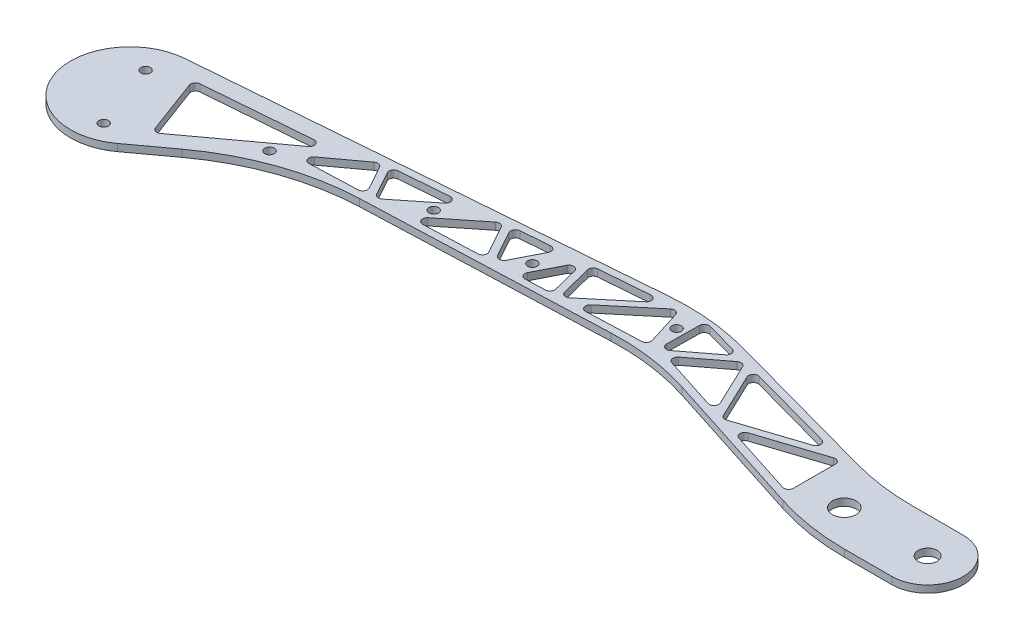
SolidWorks part; units mm, degrees
ref_plane "Front Plane" through (0, 0, 0) normal (0, 0, 1) x (1, 0, 0)
ref_plane "Top Plane" through (0, 0, 0) normal (0, 1, 0) x (1, 0, 0)
ref_plane "Right Plane" through (0, 0, 0) normal (1, 0, 0) x (0, 0, -1)
sketch "Sketch1" plane through (0, 0, 0) normal (0, 1, 0) x (1, 0, 0)
  line L0 (0, 0) -> (-300, 0) construction
  line L1 (0, 0) -> (35, 0) construction
  line L2 (0, 15) -> (35, 15)
  line L3 (0, -15) -> (35, -15)
  line L4 (-302.0128, 24.9188) -> (-285.1961, -20.1456) construction
  line L5 (-96.4179, 41.5254) -> (-717.946, -8.6774)
  line L6 (0, 15) -> (-657.0371, 195.7568)
  line L7 (0, 15) -> (-8.2094, -12.5541) construction
  line L8 (-717.946, -8.6774) -> (-94.8534, 15.2636)
  line L9 (-657.0371, 195.7568) -> (-8.2094, -12.5541)
  line L10 (-285.1961, -20.1456) -> (-244.8534, 9.5002)
  line L11 (-8.2094, -12.5541) -> (0, -15)
  circle A0 centre (0, 0) radius 5
  circle A1 centre (-300, 0) radius 25
  circle A2 centre (35, 0) radius 4
  circle A3 centre (0, 0) radius 15
  circle A4 centre (35, 0) radius 15
  dimension "D1" = 10
  dimension "D4" = 8
  dimension "D5" = 50
  dimension "D6" = 30
  dimension "D7" = 160
  dimension "D2" = 300
  dimension "D3" = 35
  dimension "D8" = 160
  dimension "D9" = 100
  dimension "D10" = 150
  dimension "D11" = 91
extrude "Boss-Extrude1" add sketch "Sketch1" along normal blind 3 contours L8 A1 | A1 L8 | A1 L8 L9 L5 | A1 L10 L8 | A3 L6 L5 L9 | A3 A0 | A4 L2 A3 L3 | A4 A2 region at (-69.8594, 0, -19.9268) region at (17.5, 0, 0) region at (10.3066, 0, -10.3066) region at (45.3066, 0, -10.3066) region at (-200.8967, 0, -21.2858) region at (-300.5642, 0, -14.6835) region at (-265.9012, 0, -0.8715) region at (-299.7406, 0, 6.7503)
fillet "Fillet1" radius 100 5 edges at (0, 1.5, -15) (-96.4179, 1.5, -41.5254) (-94.8534, 1.5, -15.2636) (-244.8534, 1.5, -9.5002) (0, 1.5, 15)
sketch "Sketch2" plane through (0, 3, 0) normal (0, 1, 0) x (1, 0, 0)
  line L0 (-285.1961, -20.1456) -> (-302.0128, 24.9188) construction
  line L1 (-292.2159, 18.6874) -> (-281.8765, -9.0194)
  line L2 (-281.8765, -9.0194) -> (-238.2394, 23.0472)
  line L3 (-238.2394, 23.0472) -> (-292.2159, 18.6874)
  line L4 (-285.1961, -20.1456) -> (-269.5743, -8.666) construction
  line L5 (-113.9933, 40.1058) -> (-302.0128, 24.9188) construction
  line L6 (-17.7547, 16.773) -> (-17.7547, -6.3387)
  line L7 (-17.7547, -6.3387) -> (-53.3654, 5.0944)
  line L8 (-53.3654, 5.0944) -> (-17.7547, 16.773)
  line L9 (-22.99, 18.2133) -> (-69.8958, 31.1175)
  line L10 (-69.8958, 31.1175) -> (-58.2301, 6.6562)
  line L11 (-58.2301, 6.6562) -> (-22.99, 18.2133)
  line L12 (-62.1547, 7.9163) -> (-73.7214, 32.17)
  line L13 (-73.7214, 32.17) -> (-92.6229, 17.6983)
  line L14 (-92.6229, 17.6983) -> (-62.1547, 7.9163)
  line L15 (-13.0208, 18.5821) -> (-79.4168, 36.8483) construction
  line L16 (-78.0647, 9.8735) -> (-15.5008, -10.2131) construction
  line L17 (-86.3511, 35.6445) -> (-12.0577, 15.2057) construction
  line L18 (-62.1547, 7.9163) -> (-53.3654, 5.0944) construction
  line L19 (-77.3519, 33.1687) -> (-96.9203, 18.1864)
  line L20 (-96.9203, 18.1864) -> (-244.1063, 12.5311) construction
  line L21 (-244.1063, 12.5311) -> (-222.6175, 28.3221)
  line L22 (-222.6175, 28.3221) -> (-96.7036, 38.4926) construction
  line L23 (-96.7036, 38.4926) -> (-77.3519, 33.1687)
  line L24 (-214.1981, 10.678) -> (-112.4731, 14.5866) construction
  line L25 (-96.7036, 38.4926) -> (-96.9203, 18.1864)
  line L26 (-106.5555, 37.6968) -> (-100.4103, 18.0523)
  line L27 (-100.4103, 18.0523) -> (-131.5203, 16.857)
  line L28 (-131.5203, 16.857) -> (-106.5555, 37.6968)
  line L29 (-111.7384, 37.2782) -> (-136.4276, 16.6684)
  line L30 (-136.4276, 16.6684) -> (-141.0342, 34.9118)
  line L31 (-141.0342, 34.9118) -> (-111.7384, 37.2782)
  line L32 (-144.0665, 34.6669) -> (-139.492, 16.5507)
  line L33 (-139.492, 16.5507) -> (-153.57, 16.0097)
  line L34 (-153.57, 16.0097) -> (-144.0665, 34.6669)
  line L35 (-153.4298, 33.9106) -> (-162.7272, 15.6579)
  line L36 (-162.7272, 15.6579) -> (-172.0207, 32.409)
  line L37 (-172.0207, 32.409) -> (-153.4298, 33.9106)
  line L38 (-175.3044, 32.1437) -> (-166.0864, 15.5288)
  line L39 (-166.0864, 15.5288) -> (-197.6515, 14.316)
  line L40 (-197.6515, 14.316) -> (-175.3044, 32.1437)
  line L41 (-222.6175, 28.3221) -> (-214.488, 13.6691)
  line L42 (-214.488, 13.6691) -> (-244.1063, 12.5311)
  line L43 (-219.3339, 28.5873) -> (-211.1288, 13.7982)
  line L44 (-211.1288, 13.7982) -> (-189.5777, 30.9908)
  line L45 (-189.5777, 30.9908) -> (-219.3339, 28.5873)
  line L46 (-194.4361, 21.9981) -> (-196.9306, 25.125) construction
  line L47 (-154.3314, 23.3279) -> (-150.7671, 21.5123) construction
  line L48 (-305.8804, 12.4012) -> (-295.3918, -15.7056) construction
  line L49 (-250.479, 9.0891) -> (-252.8476, 12.3124) construction
  circle A0 centre (-100.4103, 29.9667) radius 2
  circle A1 centre (-154.3314, 23.3279) radius 2
  circle A2 centre (-194.4361, 21.9981) radius 2
  circle A3 centre (-250.479, 9.0891) radius 2
  circle A4 centre (-305.8804, 12.4012) radius 2
  circle A5 centre (-295.3918, -15.7056) radius 2
  dimension "D14" = 4
  dimension "D25" = 4
  dimension "D1" = 7
  dimension "D2" = 7
  dimension "D3" = 7
  dimension "D4" = 3
  dimension "D5" = 3
  dimension "D6" = 3
  dimension "D7" = 3
  dimension "D8" = 32
  dimension "D9" = 3
  dimension "D10" = 3
  dimension "D11" = 3
  dimension "D12" = 3
  dimension "D13" = 5
  dimension "D15" = 3
  dimension "D16" = 3
  dimension "D17" = 3
  dimension "D18" = 3
  dimension "D19" = 8
  dimension "D20" = 8
  dimension "D21" = 4
  dimension "D22" = 4
  dimension "D23" = 8
  dimension "D24" = 30
extrude "Cut-Extrude1" cut sketch "Sketch2" against normal blind 3
fillet "Fillet2" radius 2 36 edges at (-17.7547, 1.5, 6.3387) (-17.7547, 1.5, -16.773) (-22.99, 1.5, -18.2133) (-58.2301, 1.5, -6.6562) (-69.8958, 1.5, -31.1175) (-62.1547, 1.5, -7.9163) (-92.6229, 1.5, -17.6983) (-73.7214, 1.5, -32.17) (-77.3519, 1.5, -33.1687) (-96.9203, 1.5, -18.1864) (-96.7036, 1.5, -38.4926) (-106.5555, 1.5, -37.6968) (-131.5203, 1.5, -16.857) (-100.4103, 1.5, -18.0523) (-141.0342, 1.5, -34.9118) (-136.4276, 1.5, -16.6684) (-111.7384, 1.5, -37.2782) (-153.57, 1.5, -16.0097) (-139.492, 1.5, -16.5507) (-144.0665, 1.5, -34.6669) (-172.0207, 1.5, -32.409) (-162.7272, 1.5, -15.6579) (-153.4298, 1.5, -33.9106) (-189.5777, 1.5, -30.9908) (-219.3339, 1.5, -28.5873) (-211.1288, 1.5, -13.7982) (-197.6515, 1.5, -14.316) (-175.3044, 1.5, -32.1437) (-166.0864, 1.5, -15.5288) (-214.488, 1.5, -13.6691) (-244.1063, 1.5, -12.5311) (-222.6175, 1.5, -28.3221) (-281.8765, 1.5, 9.0194) (-292.2159, 1.5, -18.6874) (-238.2394, 1.5, -23.0472) (-53.3654, 1.5, -5.0944)
